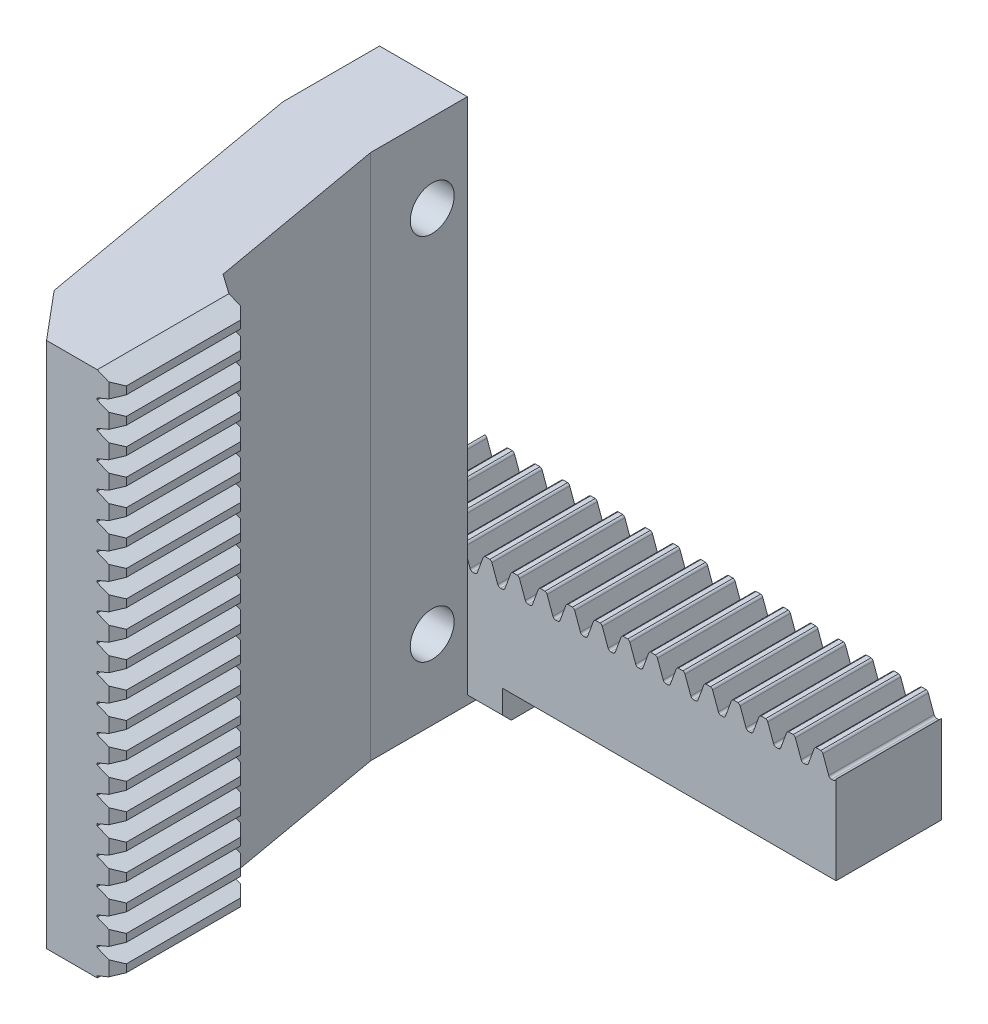
SolidWorks part; units mm, degrees
other "Markup1"
sketch "Sketch7" plane through (-50, -9.66, 16) normal (-0.9886, -0.1404, 0.0537) x (0.0542, 0, 0.9985)
ref_plane "Front Plane" through (0, 0, 0) normal (0, 0, 1) x (1, 0, 0)
ref_plane "Top Plane" through (0, 0, 0) normal (0, 1, 0) x (1, 0, 0)
ref_plane "Right Plane" through (0, 0, 0) normal (1, 0, 0) x (0, 0, -1)
sketch "Sketch1" plane through (0, 0, 0) normal (0, 0, 1) x (1, 0, 0)
  line L0 (-50, 6) -> (-50, -6) construction
  line L1 (-50, -6) -> (50, -6) construction
  line L2 (50, -6) -> (50, 6) construction
  line L4 (0, 6) -> (0, -6) construction
  line L5 (-50, 5) -> (50, 5) construction
  line L6 (-47.5453, 6) -> (-46.7025, 6) construction
  line L7 (-46.7025, 6) -> (-45.8835, 3.75) construction
  line L8 (-47.5453, 6) -> (-48.3643, 3.75) construction
  line L9 (-48.3643, 3.75) -> (-45.8835, 3.75) construction
  line L10 (-47.1239, 6) -> (-47.1239, 3.75) construction
  line L11 (-50, 0) -> (-40.8407, 0) construction
  line L12 (50, 0) -> (40.8407, 0) construction
  point P15 (-43.9823, 6)
  point P16 (-15.5, -6)
  point P17 (-46.3385, 5)
  point P18 (-47.9093, 5)
  point P21 (-0.5, -6)
  dimension "Length" = 100
  dimension "Height" = 12
  dimension "Approximate Number of Teeth" = 31
  dimension "Pressure Angle" = 20
  dimension "Circular Pitch" = 3.1416
  dimension "Addendum" = 1
  dimension "Dedendum" = 1.25
  dimension "Circular Tooth Thickness" = 1.5708
  dimension "Module" = 1
  dimension "Rack Length" = 94.2478
  dimension "D1" = 6.2832
sketch "Sketch2" plane through (0, 0, 0) normal (1, 0, 0) x (0, 0, -1)
  line L0 (-6, 0) -> (6, 0) construction
  dimension "Face Width" = 12
sketch "Sketch3" plane through (0, 0, 0) normal (0, 0, 1) x (1, 0, 0)
  line L1 (-50, 6) -> (50, 6)
  line L2 (-50, 6) -> (-50, -6)
  line L3 (-50, -6) -> (50, -6)
  line L4 (50, 6) -> (50, -6)
extrude "Boss-Extrude1" add sketch "Sketch3" against normal up to vertex (6 mm away) and the other way up to vertex (6 mm away) up to point (0, 0, -6) other way up to point (0, 0, 6)
sketch "Sketch4" plane through (0, 0, 0) normal (0, 0, 1) x (1, 0, 0)
  line L0 (-47.1239, 6) -> (-43.9823, 6) construction
  line L9 (-45.5531, 6) -> (-45.5531, 3.75)
  line L10 (-45.5531, 3.75) -> (-45.8835, 3.75)
  line L11 (-45.8835, 3.75) -> (-46.7025, 6)
  line L12 (-46.7025, 6) -> (-45.5531, 6)
  line L13 (-47.5453, 6) -> (-48.3643, 3.75)
  line L14 (-48.3643, 3.75) -> (-48.6947, 3.75)
  line L15 (-48.6947, 3.75) -> (-48.6947, 6)
  line L16 (-48.6947, 6) -> (-47.5453, 6)
  line L17 (50, 6) -> (-50, 6) construction
  line L18 (-47.5453, 6) -> (-47.3104, 6)
  line L19 (-46.9374, 6) -> (-46.7025, 6)
  arc A0 (-48.5992, 3.75) -> (-48.2839, 3.9708) centre (-48.5992, 4.0855) ccw
  arc A1 (-45.9639, 3.9708) -> (-45.6486, 3.75) centre (-45.6486, 4.0855) ccw
  arc A2 (-47.6257, 5.7792) -> (-47.3104, 6) centre (-47.3104, 5.6645) cw
  arc A3 (-46.9374, 6) -> (-46.6221, 5.7792) centre (-46.9374, 5.6645) cw
  dimension "D1" = 0.3355
extrude "Cut-Extrude1" cut sketch "Sketch4" against normal through all both and the other way through all contours L14 A0 L13 L16 L15 | L13 A2 L18 | L19 A3 L11 | L11 A1 L10 L9 L12 region at (-45.9615, 5.0903, 0) region at (-46.7355, 5.9529, 0) region at (-47.5123, 5.9529, 0) region at (-48.2863, 5.0903, 0)
pattern_linear "LPattern1" count 32 spacing 3.1416 along (1, 0, 0) count 2 spacing 3.1416 along (-1, 0, 0) of "Cut-Extrude1"
sketch "Drawing Refernce 1" plane through (0, 0, 6) normal (0, 0, 1) x (1, 0, 0)
  line L0 (-50, 0) -> (50, 0) construction
  point P6 (-35, 0)
  point P7 (-27.5, 0)
  point P8 (35, 0)
  dimension "D1" = 15
  dimension "D2" = 22.5
  dimension "D3" = 15
sketch "Sketch5" plane through (0, 0, 6) normal (0, 0, 1) x (1, 0, 0)
  line L0 (2, -6) -> (2, 23.2722) construction
  line L1 (-50, -6) -> (50, -6) construction
  line L2 (-50, 5.9906) -> (-50, -6) construction
  line L8 (2, -6) -> (50.3789, -6)
  line L9 (2, -6) -> (2, 6.3802)
  line L10 (2, 6.3802) -> (50.3789, 6.3802)
  line L11 (50.3789, -6) -> (50.3789, 6.3802)
  dimension "D1" = 52
extrude "Cut-Extrude2" cut sketch "Sketch5" against normal through all
sketch "Sketch6" plane through (0, 0, 6) normal (0, 0, 1) x (1, 0, 0)
  line L0 (-50, -6) -> (2, -6) construction
  line L1 (-50, -9.66) -> (-40, -9.66)
  line L2 (-50, -9.66) -> (-50, 50.34)
  line L3 (-50, 50.34) -> (-40, 50.34)
  line L4 (-40, -9.66) -> (-40, 50.34)
  line L5 (-50, 5.9906) -> (-50, -6) construction
  dimension "D1" = 10
  dimension "D2" = 3.66
  dimension "D3" = 60
extrude "Boss-Extrude2" add sketch "Sketch6" along normal blind 8
sketch "Sketch8" plane through (-50, 0, 0) normal (-1, 0, 0) x (0, 0, 1)
  line L1 (14, 50.34) -> (14, -9.66) construction
  line L2 (14, -9.66) -> (6, -9.66) construction
  line L3 (14, 50.34) -> (6, 50.34) construction
  circle A0 centre (10, 41.34) radius 2.5
  circle A1 centre (10, -0.66) radius 2.5
  dimension "D1" = 5
  dimension "D2" = 5
  dimension "D3" = 4
  dimension "D4" = 4
  dimension "D5" = 9
  dimension "D6" = 9
extrude "Cut-Extrude3" cut sketch "Sketch8" against normal through all
sketch "Sketch9" plane through (0, 0, 14) normal (0, 0, 1) x (1, 0, 0)
  line L0 (-40, -9.66) -> (-40, 50.34) construction
  line L1 (-50, 50.34) -> (-38.86, 50.34)
  line L2 (-50, 50.34) -> (-50, -9.66)
  line L3 (-50, -9.66) -> (-38.86, -9.66)
  line L4 (-38.86, 50.34) -> (-38.86, -9.66)
  dimension "D1" = 1.14
extrude "Boss-Extrude3" add sketch "Sketch9" along normal blind 40
sketch "Sketch10" plane through (0, -9.66, 0) normal (0, -1, 0) x (1, 0, 0)
  line L0 (-50, 44) -> (-38.86, 44) construction
  line L1 (-50, 54) -> (-50, 6) construction
  line L2 (-38.86, 54) -> (-38.86, 14) construction
  line L3 (-50, 54) -> (-38.86, 54) construction
  line L5 (-38.86, 44) -> (-38.86, 14)
  line L6 (-38.86, 14) -> (-40, 14)
  line L7 (-40, 14) -> (-40, 44)
  line L8 (-40, 44) -> (-38.86, 44)
  dimension "D1" = 10
extrude "Cut-Extrude4" cut sketch "Sketch10" against normal through all both
chamfer "Chamfer1" distance 12 angle 45 1 edges at (-45, -6, 6)
sketch "Sketch11" plane through (-50, 0, 0) normal (-1, 0, 0) x (0, 0, 1)
  line L5 (-2.34, -9.66) -> (-6, -6)
  line L6 (-6, -6) -> (-6, 5.9906)
  line L7 (-6, 5.9906) -> (6, 5.9906)
  line L8 (6, 5.9906) -> (6, 50.34)
  line L9 (48.3431, 50.34) -> (54, 44.6831)
  line L10 (54, -4.0031) -> (48.3431, -9.66)
  line L11 (43.5443, -10.137) -> (43.4726, -9.66)
  line L12 (-2.34, -9.66) -> (48.3431, -9.66)
  line L13 (6, 50.34) -> (48.3431, 50.34)
  line L14 (54, 44.6831) -> (54, -4.0031)
  circle M13 centre (10, 41.34) radius 2.5
  circle M14 centre (10, -0.66) radius 2.5
  line M15 (6, 5.9906) -> (-6, 5.9906)
  line M16 (-6, 5.9906) -> (-6, -6)
  line M17 (-6, -6) -> (-2.34, -9.66)
  line M18 (-2.34, -9.66) -> (54, -9.66)
  line M19 (54, -9.66) -> (54, 50.34)
  line M20 (54, 50.34) -> (6, 50.34)
  line M21 (6, 50.34) -> (6, 5.9906)
  dimension "D3" = 8
extrude "Cut-Extrude7" cut sketch "Sketch11" against normal blind 71 flip side to cut contours L10 L9 M19 M20 M21 M15 M16 M17 M18 M14 M13 region at (-50, 19.0116, 28.2195)
sketch "Sketch12" plane through (-40, 0, 0) normal (1, 0, 0) x (0, 0, -1)
  line L0 (-54, 44.6831) -> (-54, -9.66)
  line L1 (-44, 50.34) -> (-6, 50.34) construction
  line L2 (-17, 50.34) -> (-17, -9.66)
  line L3 (-44, -9.66) -> (2.34, -9.66) construction
  line L4 (-54, 50.34) -> (-17, 50.34)
  line L5 (-54, 44.6831) -> (-54, 50.34)
  line L7 (-54, -9.66) -> (-17, -9.66)
extrude "Cut-Extrude8" cut sketch "Sketch12" against normal blind 30 and the other way blind 30
sketch "Sketch13" plane through (0, -9.66, 0) normal (0, -1, 0) x (1, 0, 0)
  line L1 (-40, 17) -> (-36.3987, 37.4238)
  line L5 (-50, 17) -> (-40, 17)
  line L6 (-50, 17) -> (-44.4214, 48.6377)
  line L7 (-50, 17) -> (-50, 54)
  line L8 (-44.4214, 48.6377) -> (-39.9219, 54)
  line L10 (-34.1477, 39) -> (-34.1477, 54)
  line L11 (-34.1477, 54) -> (-39.9219, 54)
  line L12 (-36.3987, 37.4238) -> (-34.1477, 39)
  line M13 (-40, 17) -> (-50, 17)
  dimension "D1" = 80
  dimension "D2" = 80
  dimension "D3" = 150
  dimension "D4" = 7
  dimension "D5" = 37
  dimension "D6" = 15
  dimension "D7" = 135
extrude "Boss-Extrude4" add sketch "Sketch13" against normal blind 60 contours L1 L12 L10 L11 L8 L6 M13 region at (-41.5109, -9.66, 35.2395)
sketch "Sketch14" plane through (-51.3995, 0, 9.0631) normal (-0.9848, 0, 0.1736) x (0.1736, 0, 0.9848)
  line L0 (8.0593, 50.34) -> (8.0593, -9.66)
  line L1 (8.0593, -9.66) -> (40.1851, -9.66)
  line L2 (40.1851, -9.66) -> (40.1851, 50.34)
  line L3 (40.1851, 50.34) -> (8.0593, 50.34)
  line L4 (8.0593, 50.34) -> (9.7709, 48.7542)
  line L5 (9.7709, 48.7542) -> (38.7709, 48.7542)
  line L6 (38.7709, 48.7542) -> (40.1851, 50.34)
  line L7 (38.7709, 48.7542) -> (38.7709, -8.2458)
  line L8 (38.7709, -8.2458) -> (40.1851, -9.66)
  line L9 (38.7709, -8.2458) -> (9.7709, -8.2458)
  line L10 (9.7709, -8.2458) -> (8.0593, -9.66)
  line L11 (9.7709, -8.2458) -> (9.7709, 48.7542)
  dimension "D1" = 29
  dimension "D2" = 57
  dimension "D4" = 45
extrude "Cut-Extrude9" cut sketch "Sketch14" against normal blind 2 contours L11 L9 L7 L5 region at (-47.1849, 20.2542, 32.9652)
chamfer "Chamfer2" distance 4 angle 45 4 edges at (-48.718, -8.2458, 18.5119) (-43.6822, -8.2458, 47.0713) (-48.718, 48.7542, 18.5119) (-43.6822, 48.7542, 47.0713)
sketch "Sketch17" plane through (0, -6, 0) normal (0, -1, 0) x (1, 0, 0)
  line L0 (-40, -6) -> (-36, -6)
  line L1 (-36, -6) -> (-36, 6)
  line L2 (-40, 6) -> (2, 6) construction
  line L3 (-36, 6) -> (-40, 6)
  line L4 (-40, 6) -> (-40, -6)
  line L6 (-40, -6) -> (2, -6) construction
extrude "Boss-Extrude5" add sketch "Sketch17" along normal blind 3.66
ref_plane "Plane1" through (2, -6, -6) normal (-1, 0, 0) x (0, 0, 1)
ref_plane "Plane2" through (-40, -6, -6) normal (1, 0, 0) x (0, 0, -1)
sketch "Sketch20" plane through (0, -9.66, 0) normal (0, -1, 0) x (1, 0, 0)
  line L0 (-40, -6) -> (-50, -6)
  line L1 (-50, -6) -> (-50, -2.34)
  line L2 (-50, -2.34) -> (-40, -2.34)
  line L3 (-40, -2.34) -> (-40, -6)
extrude "Boss-Extrude6" add sketch "Sketch20" against normal blind 5.66
chamfer "Chamfer8" distance 1 angle 45 1 edges at (-38, -9.66, 6)
sketch "Sketch21" plane through (0, -9.66, 0) normal (0, -1, 0) x (1, 0, 0)
  circle A0 centre (-43, -0.5) radius 2.5
  dimension "D2" = 5
extrude "Cut-Extrude10" cut sketch "Sketch21" against normal blind 10
sketch "Sketch22" plane through (0, -9.66, 0) normal (0, -1, 0) x (1, 0, 0)
  circle A0 centre (-43, -0.5) radius 3.95
  dimension "D2" = 7.9
extrude "Cut-Extrude11" cut sketch "Sketch22" against normal blind 8
sketch "Sketch24" plane through (0, 0, 54) normal (0, 0, 1) x (1, 0, 0)
  line L0 (-34.1477, 50.34) -> (-34.1477, -9.66) construction
  line L1 (-34.1477, 50.34) -> (-34.1477, -9.66)
  line L5 (-31.8352, 49.3901) -> (-31.8352, 48.512)
  line L6 (-32.1477, 48.951) -> (-32.4598, 48.951) construction
  line L7 (-31.8352, 46.3901) -> (-31.8352, 45.512)
  line L8 (-31.8352, 43.3901) -> (-31.8352, 42.512)
  line L9 (-31.8352, 40.3901) -> (-31.8352, 39.512)
  line L10 (-31.8352, 37.3901) -> (-31.8352, 36.512)
  line L11 (-31.8352, 34.3901) -> (-31.8352, 33.512)
  line L12 (-31.8352, 31.3901) -> (-31.8352, 30.512)
  line L13 (-31.8352, 28.3901) -> (-31.8352, 27.512)
  line L14 (-31.8352, 25.3901) -> (-31.8352, 24.512)
  line L15 (-31.8352, 22.3901) -> (-31.8352, 21.512)
  line L16 (-31.8352, 19.3901) -> (-31.8352, 18.512)
  line L17 (-31.8352, 16.3901) -> (-31.8352, 15.512)
  line L18 (-31.8352, 13.3901) -> (-31.8352, 12.512)
  line L19 (-31.8352, 10.3901) -> (-31.8352, 9.512)
  line L20 (-31.8352, 7.3901) -> (-31.8352, 6.512)
  line L21 (-31.8352, 4.3901) -> (-31.8352, 3.512)
  line L22 (-31.8352, 1.3901) -> (-31.8352, 0.512)
  line L23 (-31.8352, -1.6099) -> (-31.8352, -2.488)
  line L24 (-31.8352, -4.6099) -> (-31.8352, -5.488)
  line L25 (-31.8352, -7.6099) -> (-31.8352, -8.488)
  arc A0 (-34.1477, 50.34) -> (-31.8352, 49.3901) centre (20.507, 180.1029) ccw
  arc A1 (-34.1477, 47.562) -> (-31.8352, 48.512) centre (20.507, -82.2008) cw
  arc A2 (-34.1477, 47.34) -> (-31.8352, 46.3901) centre (20.507, 177.1029) ccw
  arc A3 (-34.1477, 44.562) -> (-31.8352, 45.512) centre (20.507, -85.2008) cw
  arc A4 (-34.1477, 44.34) -> (-31.8352, 43.3901) centre (20.507, 174.1029) ccw
  arc A5 (-34.1477, 41.562) -> (-31.8352, 42.512) centre (20.507, -88.2008) cw
  arc A6 (-34.1477, 41.34) -> (-31.8352, 40.3901) centre (20.507, 171.1029) ccw
  arc A7 (-34.1477, 38.562) -> (-31.8352, 39.512) centre (20.507, -91.2008) cw
  arc A8 (-34.1477, 38.34) -> (-31.8352, 37.3901) centre (20.507, 168.1029) ccw
  arc A9 (-34.1477, 35.562) -> (-31.8352, 36.512) centre (20.507, -94.2008) cw
  arc A10 (-34.1477, 35.34) -> (-31.8352, 34.3901) centre (20.507, 165.1029) ccw
  arc A11 (-34.1477, 32.562) -> (-31.8352, 33.512) centre (20.507, -97.2008) cw
  arc A12 (-34.1477, 32.34) -> (-31.8352, 31.3901) centre (20.507, 162.1029) ccw
  arc A13 (-34.1477, 29.562) -> (-31.8352, 30.512) centre (20.507, -100.2008) cw
  arc A14 (-34.1477, 29.34) -> (-31.8352, 28.3901) centre (20.507, 159.1029) ccw
  arc A15 (-34.1477, 26.562) -> (-31.8352, 27.512) centre (20.507, -103.2008) cw
  arc A16 (-34.1477, 26.34) -> (-31.8352, 25.3901) centre (20.507, 156.1029) ccw
  arc A17 (-34.1477, 23.562) -> (-31.8352, 24.512) centre (20.507, -106.2008) cw
  arc A18 (-34.1477, 23.34) -> (-31.8352, 22.3901) centre (20.507, 153.1029) ccw
  arc A19 (-34.1477, 20.562) -> (-31.8352, 21.512) centre (20.507, -109.2008) cw
  arc A20 (-34.1477, 20.34) -> (-31.8352, 19.3901) centre (20.507, 150.1029) ccw
  arc A21 (-34.1477, 17.562) -> (-31.8352, 18.512) centre (20.507, -112.2008) cw
  arc A22 (-34.1477, 17.34) -> (-31.8352, 16.3901) centre (20.507, 147.1029) ccw
  arc A23 (-34.1477, 14.562) -> (-31.8352, 15.512) centre (20.507, -115.2008) cw
  arc A24 (-34.1477, 14.34) -> (-31.8352, 13.3901) centre (20.507, 144.1029) ccw
  arc A25 (-34.1477, 11.562) -> (-31.8352, 12.512) centre (20.507, -118.2008) cw
  arc A26 (-34.1477, 11.34) -> (-31.8352, 10.3901) centre (20.507, 141.1029) ccw
  arc A27 (-34.1477, 8.562) -> (-31.8352, 9.512) centre (20.507, -121.2008) cw
  arc A28 (-34.1477, 8.34) -> (-31.8352, 7.3901) centre (20.507, 138.1029) ccw
  arc A29 (-34.1477, 5.562) -> (-31.8352, 6.512) centre (20.507, -124.2008) cw
  arc A30 (-34.1477, 5.34) -> (-31.8352, 4.3901) centre (20.507, 135.1029) ccw
  arc A31 (-34.1477, 2.562) -> (-31.8352, 3.512) centre (20.507, -127.2008) cw
  arc A32 (-34.1477, 2.34) -> (-31.8352, 1.3901) centre (20.507, 132.1029) ccw
  arc A33 (-34.1477, -0.438) -> (-31.8352, 0.512) centre (20.507, -130.2008) cw
  arc A34 (-34.1477, -0.66) -> (-31.8352, -1.6099) centre (20.507, 129.1029) ccw
  arc A35 (-34.1477, -3.438) -> (-31.8352, -2.488) centre (20.507, -133.2008) cw
  arc A36 (-34.1477, -3.66) -> (-31.8352, -4.6099) centre (20.507, 126.1029) ccw
  arc A37 (-34.1477, -6.438) -> (-31.8352, -5.488) centre (20.507, -136.2008) cw
  arc A38 (-34.1477, -6.66) -> (-31.8352, -7.6099) centre (20.507, 123.1029) ccw
  arc A39 (-34.1477, -9.438) -> (-31.8352, -8.488) centre (20.507, -139.2008) cw
  line M8 (-34.1477, -9.66) -> (-34.1477, 50.34)
  dimension "D3" = 2.5
  dimension "D1" = 20
extrude "Boss-Extrude7" add sketch "Sketch24" against normal blind 15 contours L6 L5 A0 M8 | L5 L6 L1 A1 | L1 A3 L7 A2 | L1 A5 L8 A4 | L1 A7 L9 A6 | L1 A9 L10 A8 | L1 A11 L11 A10 | L1 A13 L12 A12 | L1 A15 L13 A14 | L1 A17 L14 A16 | L1 A19 L15 A18 | L1 A21 L16 A20 | L1 A23 L17 A22 | L1 A25 L18 A24 | L1 A27 L19 A26 | L1 A29 L20 A28 | L1 A31 L21 A30 | L1 A33 L22 A32 | L1 A35 L23 A34 | L1 A37 L24 A36 | L1 A39 L25 A38 region at (-33.1926, 48.951, 54) region at (-33.1926, -8.049, 54) region at (-33.1926, -5.049, 54) region at (-33.1926, -2.049, 54) region at (-33.1926, 0.951, 54) region at (-33.1926, 3.951, 54) region at (-33.1926, 6.951, 54) region at (-33.1926, 9.951, 54) region at (-33.1926, 12.951, 54) region at (-33.1926, 15.951, 54) region at (-33.1926, 18.951, 54) region at (-33.1926, 21.951, 54) region at (-33.1926, 24.951, 54) region at (-33.1926, 27.951, 54) region at (-33.1926, 30.951, 54) region at (-33.1926, 33.951, 54) region at (-33.1926, 36.951, 54) region at (-33.1926, 39.951, 54) region at (-33.1926, 42.951, 54) region at (-33.1926, 45.951, 54)
chamfer "Chamfer9" distance 1 angle 45 40 edges at (-31.8352, 48.951, 39) (-31.8352, 45.951, 39) (-31.8352, 42.951, 39) (-31.8352, 39.951, 39) (-31.8352, 36.951, 39) (-31.8352, 33.951, 39) (-31.8352, 30.951, 39) (-31.8352, 27.951, 39) (-31.8352, 24.951, 39) (-31.8352, 21.951, 39) (-31.8352, 18.951, 39) (-31.8352, 15.951, 39) (-31.8352, 12.951, 39) (-31.8352, 9.951, 39) (-31.8352, 6.951, 39) (-31.8352, 3.951, 39) (-31.8352, 0.951, 39) (-31.8352, -2.049, 39) (-31.8352, -5.049, 39) (-31.8352, -8.049, 39) (-31.8352, 48.951, 54) (-31.8352, 45.951, 54) (-31.8352, 42.951, 54) (-31.8352, 39.951, 54) (-31.8352, 36.951, 54) (-31.8352, 33.951, 54) (-31.8352, 30.951, 54) (-31.8352, 27.951, 54) (-31.8352, 24.951, 54) (-31.8352, 21.951, 54) (-31.8352, 18.951, 54) (-31.8352, 15.951, 54) (-31.8352, 12.951, 54) (-31.8352, 9.951, 54) (-31.8352, 6.951, 54) (-31.8352, 3.951, 54) (-31.8352, 0.951, 54) (-31.8352, -2.049, 54) (-31.8352, -5.049, 54) (-31.8352, -8.049, 54)
equation "\"Diametral Pitch\"= 1 / \"Module\""
equation "\"Pressure Angle\"=20"
equation "\"Dedendum\"= 1.25 / \"Diametral Pitch\""
equation "\"Addendum\"= 1 / \"Diametral Pitch\""
equation "\"WorkingDepth\"= 2 / \"Diametral Pitch\""
equation "\"WholeDepth\"= 2.25 / \"Diametral Pitch\""
equation "\"Clearance\"= 0.25 / \"Diametral Pitch\""
equation "\"ToothThickness\"= ( pi / 2 ) / \"Diametral Pitch\""
equation "\"CircularPitch\"= pi / \"Diametral Pitch\""
equation "\"Fillet\"= \"Clearance\" * cos ( \"Pressure Angle\" ) * tan ( ( 90 + \"Pressure Angle\" ) / 2 )"
equation "\"Module\"= 1"
equation "\"Addendum@Sketch1\"=\"Addendum\""
equation "\"Pressure Angle@Sketch1\"=\"Pressure Angle\""
equation "\"Dedendum@Sketch1\"=\"Dedendum\""
equation "\"Circular Pitch@Sketch1\"=\"CircularPitch\""
equation "\"Circular Tooth Thickness@Sketch1\"=\"ToothThickness\""
equation "\"Module@Sketch1\"=\"Module\""
equation "\"Approximate Number of Teeth@Sketch1\" = int ( \"Length@Sketch1\" /  ( 2 * \"Circular Tooth Thickness@Sketch1\" )  ) "
equation "\"Rack Length@Sketch1\" = \"Circular Pitch@Sketch1\" *  ( \"Approximate Number of Teeth@Sketch1\" - 1 ) "
equation "\"D3@LPattern1\"=\"CircularPitch\""
equation "\"D1@LPattern1\"=\"Approximate Number of Teeth@Sketch1\"+1"
equation "\"D1@Sketch1\"=\"Circular Pitch@Sketch1\"*2"
equation "\"D1@Sketch4\"=\"Fillet\""
equation "\"D4@LPattern1\"=\"CircularPitch\""
equation "\"D2@Drawing Refernce 1\"=\"D1@Drawing Refernce 1\"*1.5"
equation "\"D3@Drawing Refernce 1\"=\"D1@Drawing Refernce 1\""
